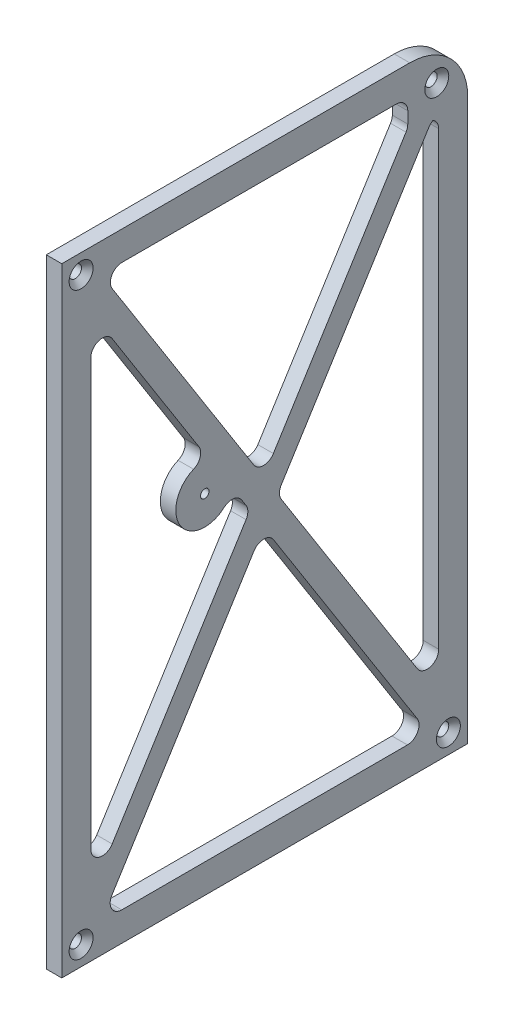
SolidWorks part; units mm, degrees
ref_plane "Front Plane" through (0, 0, 0) normal (0, 0, 1) x (1, 0, 0)
ref_plane "Top Plane" through (0, 0, 0) normal (0, 1, 0) x (1, 0, 0)
ref_plane "Right Plane" through (0, 0, 0) normal (1, 0, 0) x (0, 0, -1)
sketch "Sketch1" plane through (0, 0, 0) normal (1, 0, 0) x (0, 0, -1)
  line L1 (0, 0) -> (105, 0)
  line L2 (0, 0) -> (0, 160)
  line L3 (0, 160) -> (90, 160)
  line L4 (105, 0) -> (105, 145)
  line L8 (10.1344, 152.5) -> (89.5, 152.5)
  line L9 (97, 152) -> (5, 5) construction
  line L11 (7.5, 14.6494) -> (7.5, 145.4457)
  line L12 (5, 155) -> (100, 5) construction
  line L13 (10.1037, 7.5) -> (94.8656, 7.5)
  line L14 (44.116, 87.6309) -> (48.6727, 80.4362)
  line L16 (97.5, 14.5543) -> (97.5, 144.5)
  line L17 (0, 160) -> (131.8816, 160) construction
  line L19 (105, 0) -> (105, 197.6676) construction
  line L20 (7.5, 145.4457) -> (37.8999, 97.4458)
  line L21 (97.5, 14.5543) -> (55.7628, 80.4552)
  line L22 (90, 145) -> (117.2655, 145) construction
  line L23 (90, 145) -> (109.727, 164.727) construction
  line L24 (89.5, 152.5) -> (89.5, 145.6712)
  line L25 (95.8452, 144.5) -> (97.5, 144.5)
  line L26 (7.5, 14.6494) -> (48.6727, 80.4362)
  line L27 (10.1037, 7.5) -> (52.2328, 74.815)
  line L28 (52.2026, 86.0765) -> (89.5, 145.6712)
  line L29 (52.2026, 86.0765) -> (10.1344, 152.5)
  line L30 (55.7628, 80.4552) -> (95.8452, 144.5)
  line L31 (52.2328, 74.815) -> (94.8656, 7.5)
  circle A0 centre (5, 155) radius 1.6
  circle A1 centre (97, 152) radius 1.6
  circle A2 centre (100, 5) radius 1.6
  circle A3 centre (5, 5) radius 1.6
  arc A4 (90, 160) -> (105, 145) centre (90, 145) cw
  circle A7 centre (37, 90) radius 1.1
  arc A9 (37.8999, 97.4458) -> (44.116, 87.6309) centre (37, 90) ccw
  point P16 (5, 5)
  point P17 (5, 155)
  point P19 (96.6726, 144.5)
  point P21 (100, 5)
  dimension "D3" = 15
  dimension "D5" = 3.2
  dimension "D6" = 3.2
  dimension "D7" = 3.2
  dimension "D8" = 3.2
  dimension "D4" = 7.5
  dimension "D23" = 2.2
  dimension "D24" = 37
  dimension "D29" = 7.5
  dimension "D1" = 105
  dimension "D2" = 160
  dimension "D9" = 5
  dimension "D10" = 5
  dimension "D11" = 5
  dimension "D12" = 5
  dimension "D13" = 5
  dimension "D14" = 5
  dimension "D15" = 6
  dimension "D16" = 3
  dimension "D17" = 6
  dimension "D18" = 3
  dimension "D19" = 45
  dimension "D20" = 8
  dimension "D21" = 7.5
  dimension "D22" = 7.5
  dimension "D25" = 7.5
  dimension "D26" = 7.5
  dimension "D27" = 7.5
  dimension "D28" = 70
extrude "Boss-Extrude2" add sketch "Sketch1" along normal blind 4 contours A4 L3 L2 L1 L4 A2 A3 region at (0, 79.8958, -51.7459)
fillet "Fillet1" radius 3 16 edges at (2, 14.5543, -97.5) (2, 145.4457, -7.5) (2, 144.5, -97.5) (2, 152.5, -89.5) (2, 14.6494, -7.5) (2, 7.5, -10.1037) (2, 7.5, -94.8656) (2, 152.5, -10.1344) (2, 145.6712, -89.5) (2, 144.5, -95.8452) (2, 74.815, -52.2328) (2, 80.4552, -55.7628) (2, 86.0765, -52.2026) (2, 97.4458, -37.8999) (2, 80.4362, -48.6727) (2, 87.6309, -44.116)
chamfer "Chamfer1" distance 1.5 angle 45 4 edges at (4, 5, -101.6) (4, 5, -6.6) (4, 152, -98.6) (4, 155, -6.6)
